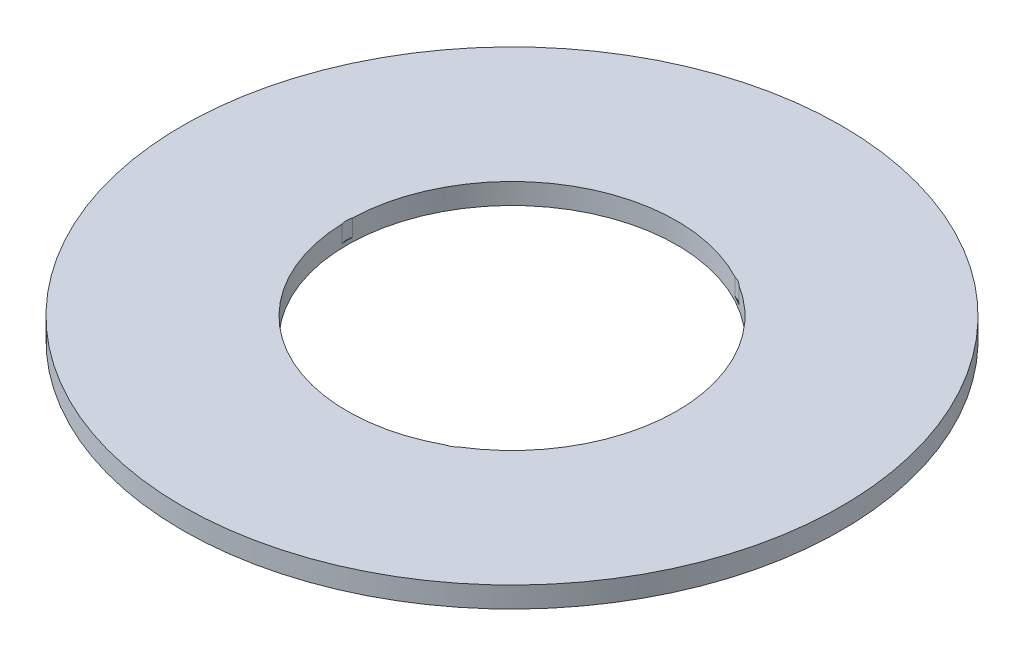
SolidWorks part; units mm, degrees
ref_plane "Front Plane" through (0, 0, 0) normal (0, 0, 1) x (1, 0, 0)
ref_plane "Top Plane" through (0, 0, 0) normal (0, 1, 0) x (1, 0, 0)
ref_plane "Right Plane" through (0, 0, 0) normal (1, 0, 0) x (0, 0, -1)
sketch "Sketch1" plane through (0, 0, 0) normal (0, 1, 0) x (1, 0, 0)
  circle A0 centre (0, 0) radius 95
  dimension "FLANGE_OD" = 190
extrude "Boss-Extrude1" add sketch "Sketch1" along normal blind 6
sketch "Sketch2" plane through (0, 0, 0) normal (0, 1, 0) x (1, 0, 0)
  circle A0 centre (0, 0) radius 47.5
  dimension "BORE_D" = 95
extrude "Cut-Extrude1" cut sketch "Sketch2" along normal through all
sketch "Sketch3" plane through (0, 6, 0) normal (0, 1, 0) x (1, 0, 0)
  circle A0 centre (0, 0) radius 42.1397 construction
  circle A1 centre (-42.1397, 0) radius 5.5464
  dimension "BOLT_D" = 11.0928
  dimension "BOLT_PCD" = 84.2793
extrude "Cut-Extrude2" cut sketch "Sketch3" against normal blind 4.8613
pattern_circular "CirPattern1" count 3 over 360 about axis through (0, 0, 0) along (0, 1, 0) of "Cut-Extrude2"
